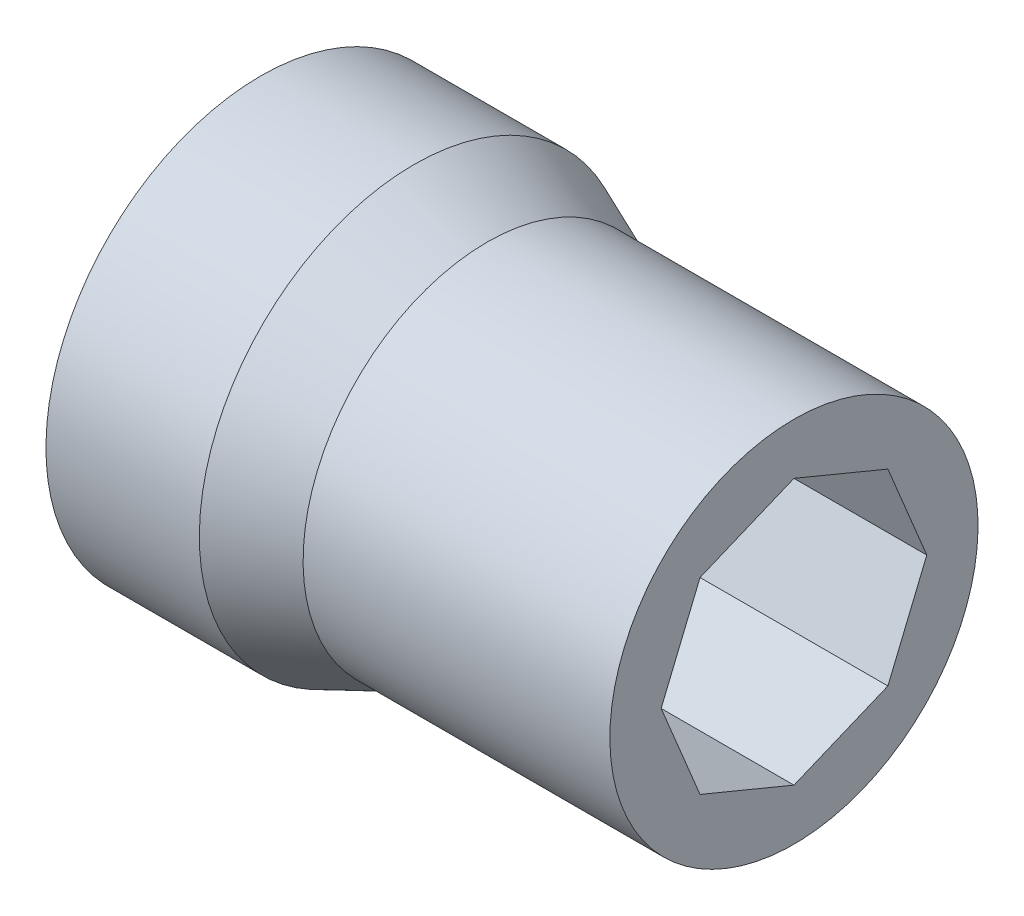
SolidWorks part; units mm, degrees
ref_plane "Front Plane" through (0, 0, 0) normal (0, 0, 1) x (1, 0, 0)
ref_plane "Top Plane" through (0, 0, 0) normal (0, 1, 0) x (1, 0, 0)
ref_plane "Right Plane" through (0, 0, 0) normal (1, 0, 0) x (0, 0, -1)
sketch "Sketch4" plane through (0, 0, 0) normal (0, 0, 1) x (1, 0, 0)
  line L0 (0, 0) -> (-5, 0)
  line L1 (-5, 0) -> (-5, 3.5)
  line L6 (-1.3094, 3) -> (0, 3)
  line L8 (-5, 3.5) -> (-2.5, 3.5)
  line L9 (-1.3094, 3) -> (-2.5, 3.5)
  line L10 (-1.3094, 3) -> (3.6906, 3) construction
  line L11 (-1.3094, 3) -> (3.6906, 3)
  line L12 (3.6906, 3) -> (3.6906, 0)
  line L13 (0, 0) -> (3.6906, 0)
  dimension "D1" = 3.5
  dimension "D2" = 3
  dimension "D3" = 3.5
revolve "Revolve4" add sketch "Sketch4" angle 360 about L0 region at (-0.8104, 1.5972, 0)
sketch "Sketch6" plane through (3.6906, 0, 0) normal (1, 0, 0) x (0, 0, -1)
  line L1 (-2.1648, 0) -> (-1.5307, -1.5307)
  line L2 (-1.5307, -1.5307) -> (0, -2.1648)
  line L3 (0, -2.1648) -> (1.5307, -1.5307)
  line L4 (1.5307, -1.5307) -> (2.1648, 0)
  line L5 (2.1648, 0) -> (1.5307, 1.5307)
  line L6 (1.5307, 1.5307) -> (0, 2.1648)
  line L7 (0, 2.1648) -> (-1.5307, 1.5307)
  line L8 (-1.5307, 1.5307) -> (-2.1648, 0)
  circle A0 centre (0, 0) radius 2 construction
extrude "Cut-Extrude2" cut sketch "Sketch6" against normal blind 4
